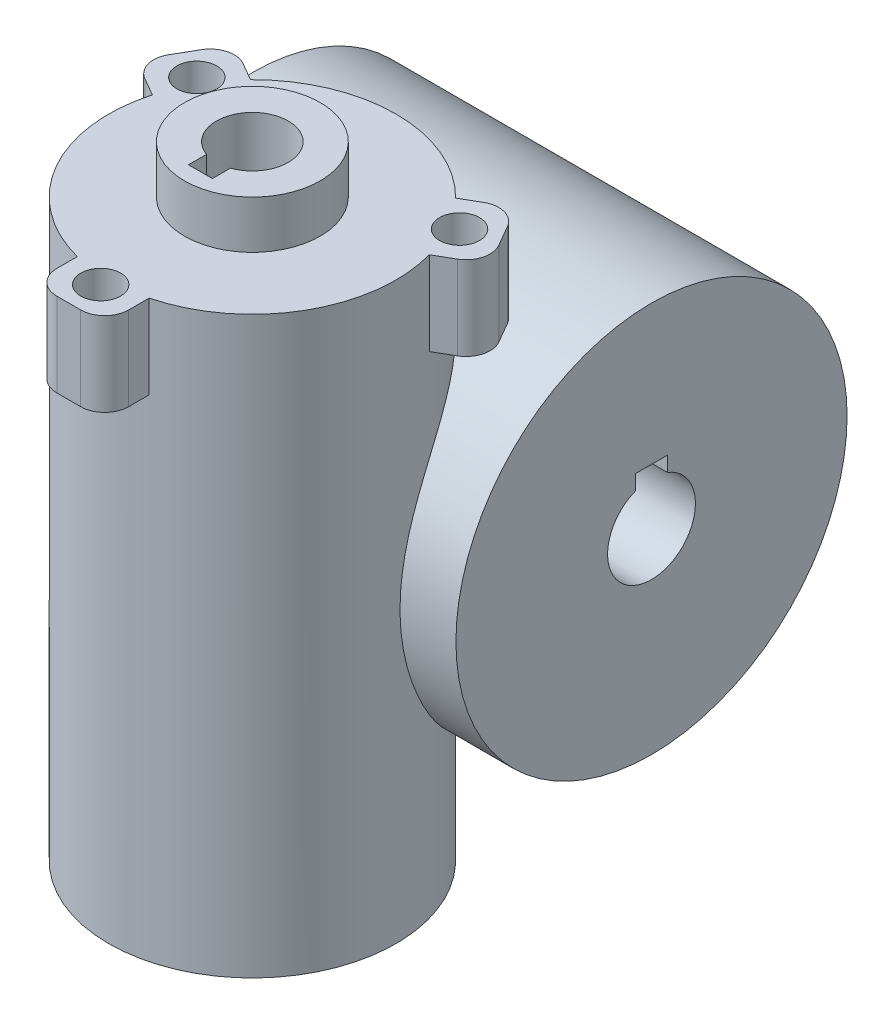
SolidWorks part; units mm, degrees
ref_plane "前视基准面" through (0, 0, 0) normal (0, 0, 1) x (1, 0, 0)
ref_plane "上视基准面" through (0, 0, 0) normal (0, 1, 0) x (1, 0, 0)
ref_plane "右视基准面" through (0, 0, 0) normal (1, 0, 0) x (0, 0, -1)
sketch "草图1" plane through (0, 0, 0) normal (0, 1, 0) x (1, 0, 0)
  circle A0 centre (0, 0) radius 18
  dimension "D1" = 36
extrude "凸台-拉伸1" add sketch "草图1" along normal blind 72
sketch "草图2" plane through (0, 0, 0) normal (1, 0, 0) x (0, 0, -1)
  line L0 (0, 0) -> (0, 72) construction
  line L1 (18, 72) -> (-18, 72) construction
  line L2 (0, 36) -> (25, 36) construction
  circle A0 centre (25, 36) radius 24.5
  dimension "D2" = 49
  dimension "D1" = 25
extrude "凸台-拉伸2" add sketch "草图2" along normal blind 25 and the other way blind 25
sketch "草图3" plane through (25, 0, 0) normal (1, 0, 0) x (0, 0, -1)
  line L2 (23, 41.1235) -> (23, 43)
  line L3 (23, 43) -> (27, 43)
  line L4 (27, 41.1235) -> (27, 43)
  line L5 (23.489, 30.7116) -> (27, 43) construction
  line L6 (23, 43) -> (26.511, 30.7116) construction
  arc A0 (23, 41.1235) -> (27, 41.1235) centre (25, 36) ccw
  dimension "D1" = 11
  dimension "D2" = 4
  dimension "D3" = 7
extrude "切除-拉伸1" cut sketch "草图3" against normal through all
sketch "草图4" plane through (0, 72, 0) normal (0, 1, 0) x (1, 0, 0)
  line L2 (-1.5, -4.2426) -> (-1.5, -6.5)
  line L3 (-1.5, -6.5) -> (1.5, -6.5)
  line L4 (1.5, -4.2426) -> (1.5, -6.5)
  line L5 (-1.0119, 4.3848) -> (1.5, -6.5) construction
  line L6 (-1.5, -6.5) -> (1.0119, 4.3848) construction
  arc A0 (1.5, -4.2426) -> (-1.5, -4.2426) centre (0, 0) ccw
  dimension "D1" = 9
  dimension "D3" = 6.5
sketch "草图5" plane through (0, 72, 0) normal (0, 1, 0) x (1, 0, 0)
  circle A0 centre (0, 0) radius 8.5
  dimension "D1" = 17
extrude "凸台-拉伸3" add sketch "草图5" along normal blind 6
extrude "切除-拉伸2" cut sketch "草图4" against normal blind 12 and the other way blind 10
sketch "草图6" plane through (0, 72, 0) normal (0, 1, 0) x (1, 0, 0)
  line L0 (-20.6686, 10.201) -> (-19.1686, 12.799)
  line L1 (1.5, -23) -> (-1.5, -23)
  line L2 (4.5, -20) -> (4.5, -17.4284)
  line L3 (-19.5705, 6.1029) -> (-17.3435, 4.8171)
  line L4 (-4.5, -20) -> (-4.5, -17.4284)
  line L5 (4.5, -23) -> (-4.5, -15) construction
  line L6 (4.5, -15) -> (-4.5, -23) construction
  line L7 (-15.0705, 13.8971) -> (-12.8435, 12.6113)
  line L8 (-22.1686, 7.6029) -> (-10.7404, 11.3971) construction
  line L9 (-15.2404, 3.6029) -> (-17.6686, 15.3971) construction
  line L10 (19.1686, 12.799) -> (20.6686, 10.201)
  line L11 (15.0705, 13.8971) -> (12.8435, 12.6113)
  line L12 (19.5705, 6.1029) -> (17.3435, 4.8171)
  line L13 (17.6686, 15.3971) -> (15.2404, 3.6029) construction
  line L14 (10.7404, 11.3971) -> (22.1686, 7.6029) construction
  circle A0 centre (0, 0) radius 19 construction
  arc A1 (-4.5, -20) -> (-1.5, -23) centre (-1.5, -20) ccw
  arc A2 (4.5, -20) -> (1.5, -23) centre (1.5, -20) cw
  arc A3 (-15.0705, 13.8971) -> (-19.1686, 12.799) centre (-16.5705, 11.299) ccw
  arc A4 (-4.5, -17.4284) -> (4.5, -17.4284) centre (0, 0) ccw
  arc A5 (-19.5705, 6.1029) -> (-20.6686, 10.201) centre (-18.0705, 8.701) cw
  arc A6 (-12.8435, 12.6113) -> (-17.3435, 4.8171) centre (0, 0) ccw
  arc A7 (19.5705, 6.1029) -> (20.6686, 10.201) centre (18.0705, 8.701) ccw
  arc A8 (15.0705, 13.8971) -> (19.1686, 12.799) centre (16.5705, 11.299) cw
  arc A9 (17.3435, 4.8171) -> (12.8435, 12.6113) centre (0, 0) ccw
  point P3 (0, -19)
  point P19 (-16.4545, 9.5)
  point P32 (16.4545, 9.5)
  point P45 (0, 0)
  dimension "D1" = 38
  dimension "D4" = 3
  dimension "D5" = 3
  dimension "D2" = 8
  dimension "D3" = 9
extrude "凸台-拉伸4" add sketch "草图6" against normal blind 10.5
sketch "草图7" plane through (0, 72, 0) normal (0, 1, 0) x (1, 0, 0)
  circle A0 centre (0, -19) radius 2.5
  circle A1 centre (16.4545, 9.5) radius 2.5
  circle A2 centre (-16.4545, 9.5) radius 2.5
  dimension "D1" = 5
extrude "切除-拉伸3" cut sketch "草图7" against normal blind 5
